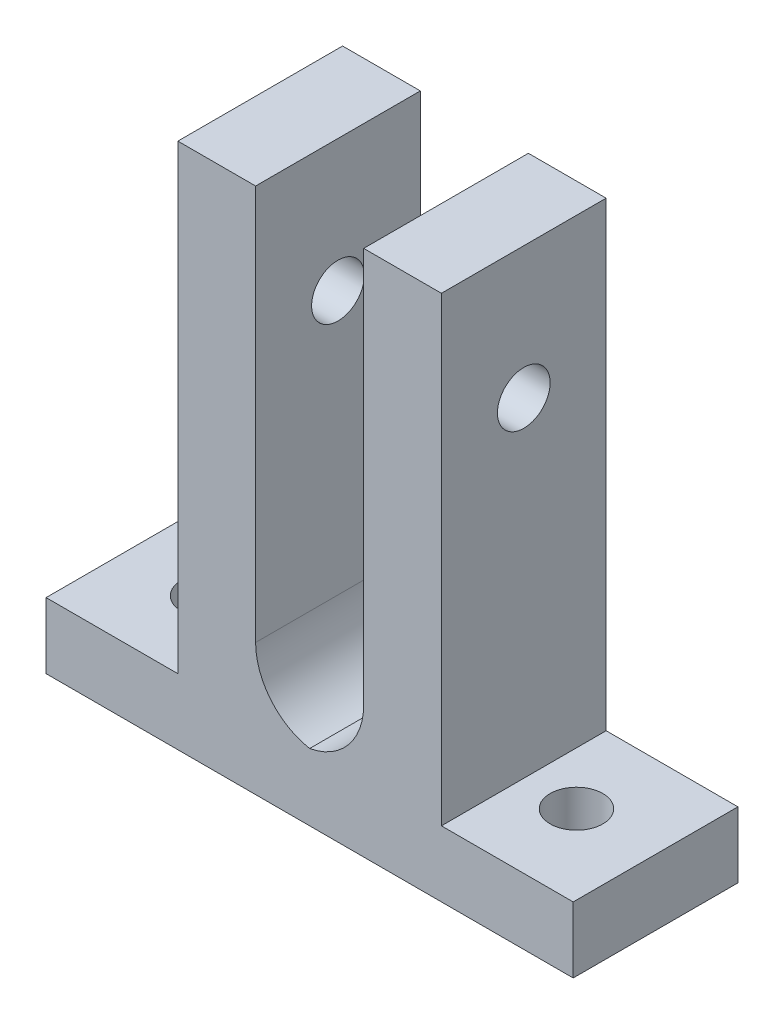
SolidWorks part; units mm, degrees
ref_plane "Спереди" through (0, 0, 0) normal (0, 0, 1) x (1, 0, 0)
ref_plane "Сверху" through (0, 0, 0) normal (0, 1, 0) x (1, 0, 0)
ref_plane "Справа" through (0, 0, 0) normal (1, 0, 0) x (0, 0, -1)
sketch "Эскиз1" plane through (0, 0, 0) normal (0, 0, 1) x (1, 0, 0)
  line L0 (0, 0) -> (0, 5)
  line L1 (0, 5) -> (10, 5)
  line L2 (10, 5) -> (10, 40)
  line L3 (10, 40) -> (15.9, 40)
  line L4 (15.9, 40) -> (15.9, 5)
  line L5 (15.9, 5) -> (24.1, 5)
  line L6 (24.1, 5) -> (24.1, 40)
  line L7 (24.1, 40) -> (30, 40)
  line L8 (30, 40) -> (30, 5)
  line L9 (30, 5) -> (40, 5)
  line L10 (40, 5) -> (40, 0)
  line L11 (40, 0) -> (0, 0)
  dimension "D1" = 20
  dimension "D2" = 40
  dimension "D3" = 8.2
  dimension "D4" = 5
  dimension "D5" = 35
extrude "Вытянуть1" add sketch "Эскиз1" along normal blind 12.5
sketch "Эскиз2" plane through (10, 0, 0) normal (-1, 0, 0) x (0, 0, 1)
  line L0 (12.5, 40) -> (0, 40) construction
  circle A0 centre (6.25, 30) radius 2
  point P4 (6.25, 40)
  dimension "D1" = 4
  dimension "D2" = 10
extrude "Вытянуть2" cut sketch "Эскиз2" against normal through all
sketch "Эскиз3" plane through (0, 5, 0) normal (0, 1, 0) x (1, 0, 0)
  line L1 (40, -12.5) -> (40, 0) construction
  line L3 (20, 0) -> (20, -12.5) construction
  line L4 (24.1, 0) -> (15.9, 0) construction
  line L5 (24.1, -12.5) -> (15.9, -12.5) construction
  circle A0 centre (34, -6.25) radius 2
  circle A1 centre (6, -6.25) radius 2
  point P1 (40, -6.25)
  dimension "D1" = 4
  dimension "D2" = 14
  dimension "D3" = 14
extrude "Вытянуть3" cut sketch "Эскиз3" against normal up to next
fillet "Скругление1" radius 5 2 edges at (24.1, 5, 6.25) (15.9, 5, 6.25)
